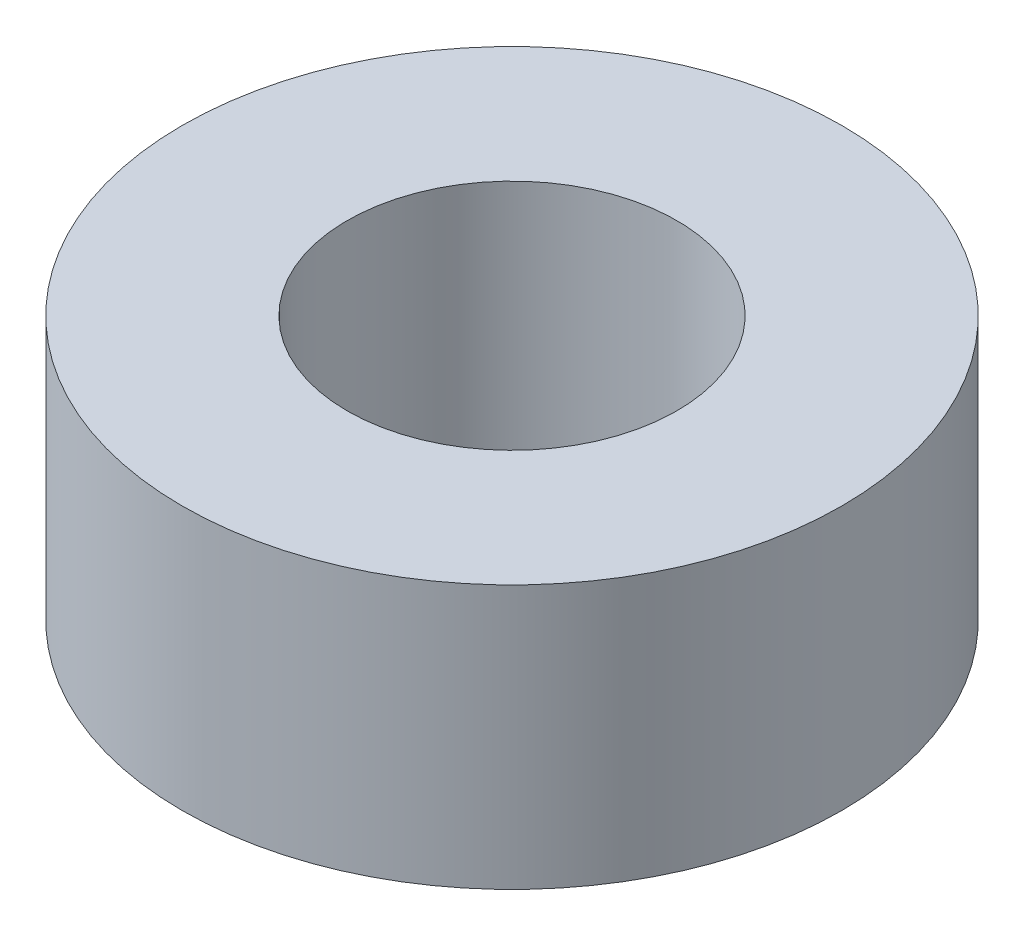
SolidWorks part; units mm, degrees
ref_plane "Front Plane" through (0, 0, 0) normal (0, 0, 1) x (1, 0, 0)
ref_plane "Top Plane" through (0, 0, 0) normal (0, 1, 0) x (1, 0, 0)
ref_plane "Right Plane" through (0, 0, 0) normal (1, 0, 0) x (0, 0, -1)
sketch "Sketch1" plane through (0, 0, 0) normal (0, 1, 0) x (1, 0, 0)
  circle A0 centre (0, 0) radius 15
  dimension "FLANGE_OD" = 30
extrude "Boss-Extrude1" add sketch "Sketch1" along normal blind 12
sketch "Sketch2" plane through (0, 0, 0) normal (0, 1, 0) x (1, 0, 0)
  circle A0 centre (0, 0) radius 7.5
  dimension "BORE_D" = 15
extrude "Cut-Extrude1" cut sketch "Sketch2" along normal through all
sketch "Sketch3" plane through (0, 12, 0) normal (0, 1, 0) x (1, 0, 0)
  circle A0 centre (0, 0) radius 5.5225 construction
  circle A1 centre (-5.5225, 0) radius 1.5
  dimension "BOLT_D" = 3
  dimension "BOLT_PCD" = 11.045
extrude "Cut-Extrude2" cut sketch "Sketch3" against normal blind 10.1726 rebuild error yes
pattern_circular "CirPattern1" count 5 over 360 rebuild error yes
